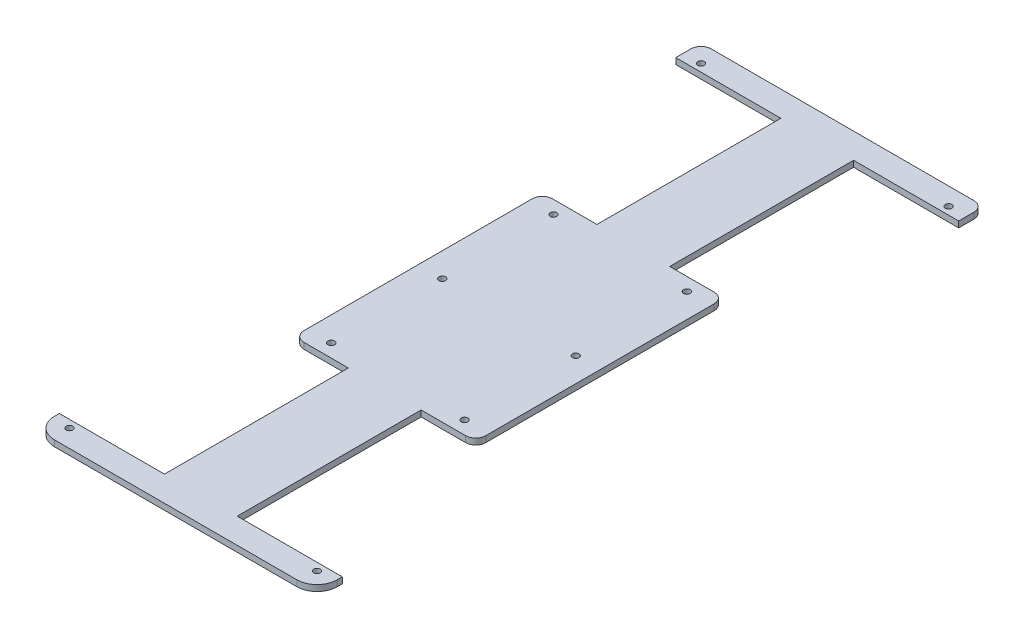
SolidWorks part; units mm, degrees
ref_plane "Front Plane" through (0, 0, 0) normal (0, 0, 1) x (1, 0, 0)
ref_plane "Top Plane" through (0, 0, 0) normal (0, 1, 0) x (1, 0, 0)
ref_plane "Right Plane" through (0, 0, 0) normal (1, 0, 0) x (0, 0, -1)
sketch "Sketch1" plane through (0, 0, 0) normal (0, 1, 0) x (1, 0, 0)
  line L0 (0, 0) -> (140, 0)
  line L1 (0, 0) -> (140, 0) construction
  line L2 (0, 0) -> (0, 330) construction
  line L3 (0, 330) -> (140, 330) construction
  line L4 (140, 0) -> (140, 330) construction
  line L5 (140, 0) -> (140, 12.5)
  line L6 (140, 12.5) -> (88, 12.5)
  line L7 (88, 12.5) -> (88, 103.5)
  line L11 (88, 226.5) -> (88, 317.5)
  line L12 (88, 317.5) -> (140, 317.5)
  line L13 (140, 317.5) -> (140, 330)
  line L14 (140, 330) -> (0, 330)
  line L15 (0, 330) -> (0, 317.5)
  line L16 (0, 317.5) -> (52, 317.5)
  line L17 (52, 317.5) -> (52, 226.5)
  line L21 (52, 103.5) -> (52, 12.5)
  line L22 (52, 12.5) -> (0, 12.5)
  line L23 (0, 12.5) -> (0, 0)
  line L24 (52, 226.5) -> (25, 226.5)
  line L25 (25, 226.5) -> (25, 103.5)
  line L26 (25, 103.5) -> (52, 103.5)
  line L27 (88, 226.5) -> (115, 226.5)
  line L28 (115, 226.5) -> (115, 103.5)
  line L29 (115, 103.5) -> (88, 103.5)
  dimension "D1" = 140
  dimension "D2" = 330
  dimension "D3" = 52
  dimension "D4" = 91
  dimension "D5" = 25
  dimension "D6" = 123
extrude "Boss-Extrude1" add sketch "Sketch1" along normal blind 3
fillet "Fillet1" radius 10 2 edges at (140, 1.5, 0) (0, 1.5, 0)
fillet "Fillet2" radius 5 6 edges at (0, 1.5, -330) (140, 1.5, -330) (115, 1.5, -226.5) (115, 1.5, -103.5) (25, 1.5, -103.5) (25, 1.5, -226.5)
sketch "Sketch2" plane through (0, 3, 0) normal (0, 1, 0) x (1, 0, 0)
  line L2 (37, 220) -> (37, 110) construction
  line L3 (25, 165) -> (37, 165) construction
  line L4 (25, 221.5) -> (25, 108.5) construction
  line L5 (70, 330) -> (70, 0) construction
  line L6 (135, 330) -> (5, 330) construction
  line L7 (10, 0) -> (130, 0) construction
  circle A0 centre (37, 220) radius 1.65
  circle A1 centre (37, 165) radius 1.65
  circle A2 centre (37, 110) radius 1.65
  circle A3 centre (103, 110) radius 1.65
  circle A4 centre (103, 165) radius 1.65
  circle A5 centre (103, 220) radius 1.65
  dimension "D3" = 3.3
  dimension "D1" = 12
  dimension "D2" = 110
extrude "Cut-Extrude1" cut sketch "Sketch2" against normal through all
sketch "Sketch3" plane through (0, 3, 0) normal (0, 1, 0) x (1, 0, 0)
  line L0 (0, 12.5) -> (8.75, 12.5) construction
  line L1 (52, 12.5) -> (0, 12.5) construction
  line L2 (8.75, 12.5) -> (8.75, 8.75) construction
  line L3 (70, 0) -> (70, 57.6288) construction
  line L4 (10, 0) -> (130, 0) construction
  circle A0 centre (8.75, 8.75) radius 1.65
  circle A1 centre (131.25, 8.75) radius 1.65
  dimension "D3" = 3.3
  dimension "D1" = 8.75
  dimension "D2" = 3.75
extrude "Cut-Extrude2" cut sketch "Sketch3" against normal through all
sketch "Sketch4" plane through (0, 3, 0) normal (0, 1, 0) x (1, 0, 0)
  line L0 (0, 317.5) -> (8.75, 317.5) construction
  line L1 (0, 317.5) -> (52, 317.5) construction
  line L2 (8.75, 317.5) -> (8.75, 321.25) construction
  line L3 (70, 330) -> (70, 288.2737) construction
  line L4 (135, 330) -> (5, 330) construction
  circle A0 centre (8.75, 321.25) radius 1.65
  circle A1 centre (131.25, 321.25) radius 1.65
  dimension "D3" = 3.3
  dimension "D1" = 8.75
  dimension "D2" = 3.75
extrude "Cut-Extrude3" cut sketch "Sketch4" against normal through all
